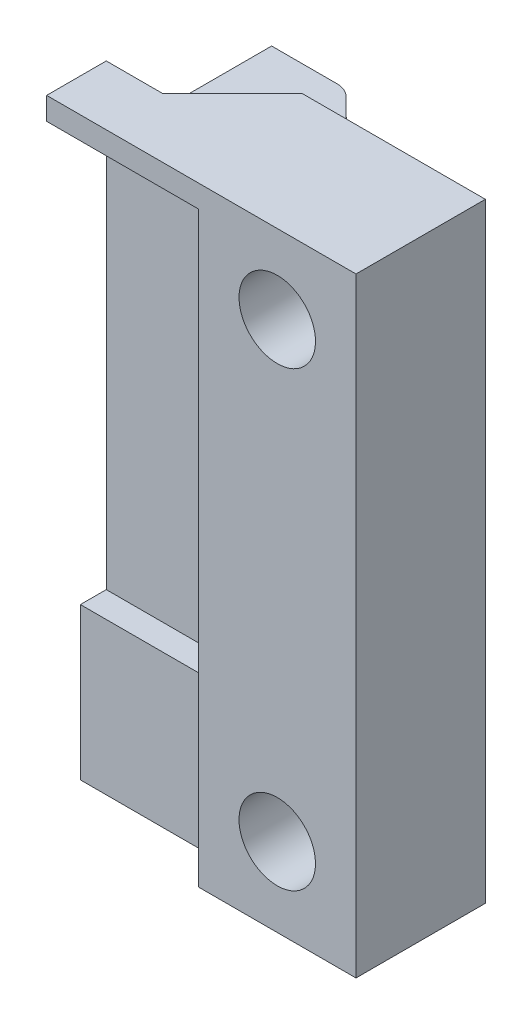
SolidWorks part; units mm, degrees
ref_plane "Front Plane" through (0, 0, 0) normal (0, 0, 1) x (1, 0, 0)
ref_plane "Top Plane" through (0, 0, 0) normal (0, 1, 0) x (1, 0, 0)
ref_plane "Right Plane" through (0, 0, 0) normal (1, 0, 0) x (0, 0, -1)
sketch "Sketch1" plane through (0, 0, 0) normal (0, 0, 1) x (1, 0, 0)
  line L0 (93.7285, 63.9679) -> (92.0785, 63.9679) construction
  line L1 (93.7285, 63.9679) -> (95.7285, 63.9679) construction
  line L2 (96.7285, 63.9679) -> (95.7285, 63.9679) construction
  line L3 (-96.2715, 63.9679) -> (-97.2715, 63.9679) construction
  line L4 (-96.2715, 63.9679) -> (-94.2715, 63.9679) construction
  line L5 (-92.6215, 63.9679) -> (-94.2715, 63.9679) construction
  line L6 (93.7285, 63.9679) -> (92.0785, 63.9679)
  line L7 (93.7285, 63.9679) -> (95.7285, 63.9679)
  line L8 (96.7285, 63.9679) -> (95.7285, 63.9679)
  line L9 (-96.2715, 63.9679) -> (-97.2715, 63.9679)
  line L10 (-96.2715, 63.9679) -> (-94.2715, 63.9679)
  line L11 (-92.6215, 63.9679) -> (-94.2715, 63.9679)
  line L12 (94.7285, 38.5679) -> (83.2213, 38.5679)
  line L13 (94.7285, 38.5679) -> (83.2213, 38.5679)
  line L14 (82.5285, 37.9679) -> (-69.3016, 37.9679)
  line L15 (82.5285, 37.9679) -> (-69.3016, 37.9679)
  line L16 (-69.3016, 37.9679) -> (-74.3016, 37.9679)
  line L17 (-69.3016, 37.9679) -> (-74.3016, 37.9679)
  line L18 (-74.3016, 37.9679) -> (-84.5715, 37.9679)
  line L19 (-74.3016, 37.9679) -> (-84.5715, 37.9679)
  line L20 (-84.5715, 37.9679) -> (-85.2715, 37.9679)
  line L21 (-84.5715, 37.9679) -> (-85.2715, 37.9679)
  line L22 (-85.2715, 37.9679) -> (-85.2715, 38.5679)
  line L23 (-85.2715, 37.9679) -> (-85.2715, 38.5679)
  line L24 (-85.2715, 38.5679) -> (-95.2715, 38.5679)
  line L25 (-85.2715, 38.5679) -> (-95.2715, 38.5679)
  line L26 (-97.2715, 40.5679) -> (-97.2715, 44.9679)
  line L27 (-97.2715, 40.5679) -> (-97.2715, 44.9679)
  line L28 (-97.2715, 44.9679) -> (-97.2715, 45.9679)
  line L29 (-97.2715, 44.9679) -> (-97.2715, 45.9679)
  line L30 (-97.2715, 45.9679) -> (-97.2715, 46.2179)
  line L31 (-97.2715, 45.9679) -> (-97.2715, 46.2179)
  line L32 (-97.2715, 46.2179) -> (-97.2715, 47.2179)
  line L33 (-97.2715, 46.2179) -> (-97.2715, 47.2179)
  line L34 (-97.2715, 47.2179) -> (-97.2715, 47.4679)
  line L35 (-97.2715, 47.2179) -> (-97.2715, 47.4679)
  line L36 (-97.2715, 47.4679) -> (-97.2715, 48.4679)
  line L37 (-97.2715, 47.4679) -> (-97.2715, 48.4679)
  line L38 (-97.2715, 48.4679) -> (-97.2715, 48.7179)
  line L39 (-97.2715, 48.4679) -> (-97.2715, 48.7179)
  line L40 (-97.2715, 48.7179) -> (-97.2715, 49.7179)
  line L41 (-97.2715, 48.7179) -> (-97.2715, 49.7179)
  line L42 (-97.2715, 49.7179) -> (-97.2715, 49.9679)
  line L43 (-97.2715, 49.7179) -> (-97.2715, 49.9679)
  line L44 (-97.2715, 49.9679) -> (-97.2715, 50.9679)
  line L45 (-97.2715, 49.9679) -> (-97.2715, 50.9679)
  line L46 (-97.2715, 50.9679) -> (-97.2715, 51.2179)
  line L47 (-97.2715, 50.9679) -> (-97.2715, 51.2179)
  line L48 (-97.2715, 51.2179) -> (-97.2715, 52.2179)
  line L49 (-97.2715, 51.2179) -> (-97.2715, 52.2179)
  line L50 (-97.2715, 52.2179) -> (-97.2715, 52.4679)
  line L51 (-97.2715, 52.2179) -> (-97.2715, 52.4679)
  line L52 (-97.2715, 52.4679) -> (-97.2715, 53.4679)
  line L53 (-97.2715, 52.4679) -> (-97.2715, 53.4679)
  line L54 (-97.2715, 53.4679) -> (-97.2715, 53.7179)
  line L55 (-97.2715, 53.4679) -> (-97.2715, 53.7179)
  line L56 (-97.2715, 53.7179) -> (-97.2715, 54.7179)
  line L57 (-97.2715, 53.7179) -> (-97.2715, 54.7179)
  line L58 (-97.2715, 54.7179) -> (-97.2715, 54.9679)
  line L59 (-97.2715, 54.7179) -> (-97.2715, 54.9679)
  line L60 (-97.2715, 54.9679) -> (-97.2715, 55.9679)
  line L61 (-97.2715, 54.9679) -> (-97.2715, 55.9679)
  line L62 (-97.2715, 55.9679) -> (-97.2715, 56.2179)
  line L63 (-97.2715, 55.9679) -> (-97.2715, 56.2179)
  line L64 (-97.2715, 56.2179) -> (-97.2715, 57.2179)
  line L65 (-97.2715, 56.2179) -> (-97.2715, 57.2179)
  line L66 (-97.2715, 57.2179) -> (-97.2715, 57.4679)
  line L67 (-97.2715, 57.2179) -> (-97.2715, 57.4679)
  line L68 (-97.2715, 57.4679) -> (-97.2715, 58.4679)
  line L69 (-97.2715, 57.4679) -> (-97.2715, 58.4679)
  line L70 (-97.2715, 58.4679) -> (-97.2715, 58.7179)
  line L71 (-97.2715, 58.4679) -> (-97.2715, 58.7179)
  line L72 (-97.2715, 58.7179) -> (-97.2715, 59.7179)
  line L73 (-97.2715, 58.7179) -> (-97.2715, 59.7179)
  line L74 (-97.2715, 59.7179) -> (-97.2715, 59.9679)
  line L75 (-97.2715, 59.7179) -> (-97.2715, 59.9679)
  line L76 (-97.2715, 59.9679) -> (-97.2715, 61.9679)
  line L77 (-97.2715, 59.9679) -> (-97.2715, 61.9679)
  line L78 (-97.2715, 61.9679) -> (-97.2715, 63.9679)
  line L79 (-97.2715, 61.9679) -> (-97.2715, 63.9679)
  line L80 (-97.2715, 63.9679) -> (96.7285, 63.9679)
  line L81 (-97.2715, 63.9679) -> (96.7285, 63.9679)
  line L82 (96.7285, 63.9679) -> (96.7285, 61.9679)
  line L83 (96.7285, 63.9679) -> (96.7285, 61.9679)
  line L84 (96.7285, 61.9679) -> (96.7285, 40.5679)
  line L85 (96.7285, 61.9679) -> (96.7285, 40.5679)
  arc A0 (82.5285, 37.9679) -> (83.2213, 38.5679) centre (82.5285, 38.6679) ccw
  arc A1 (82.5285, 37.9679) -> (83.2213, 38.5679) centre (82.5285, 38.6679) ccw
  arc A2 (-97.2715, 40.5679) -> (-95.2715, 38.5679) centre (-95.2715, 40.5679) ccw
  arc A3 (-97.2715, 40.5679) -> (-95.2715, 38.5679) centre (-95.2715, 40.5679) ccw
  arc A4 (94.7285, 38.5679) -> (96.7285, 40.5679) centre (94.7285, 40.5679) ccw
  arc A5 (94.7285, 38.5679) -> (96.7285, 40.5679) centre (94.7285, 40.5679) ccw
sketch "Sketch2" plane through (0, 0, 0) normal (0, 1, 0) x (1, 0, 0)
  line L30 (94, 0) -> (97, 0) construction
  line L54 (0, -21) -> (0, 21) construction
  line L56 (-94, 0) -> (-97, 0) construction
  line L57 (-94, -21) -> (94, -21) construction
  line L58 (-94, -21) -> (-94, 21) construction
  line L59 (-94, 21) -> (94, 21) construction
  line L60 (94, -21) -> (94, 21) construction
  line L61 (97, -27.5) -> (-97, -27.5) construction
  line L62 (97, -27.5) -> (97, 27.5) construction
  line L63 (97, 27.5) -> (-97, 27.5) construction
  line L64 (-97, -27.5) -> (-97, 27.5) construction
  line L65 (91, 24.625) -> (91, 17.375)
  line L66 (91, -24.625) -> (97, -24.625)
  line L67 (91, -24.625) -> (91, -17.375)
  line L68 (91, -17.375) -> (97, -17.375)
  line L69 (97, -24.625) -> (97, -17.375) construction
  line L70 (91, -24.625) -> (97, -17.375) construction
  line L71 (91, -17.375) -> (97, -24.625) construction
  line L72 (91, 24.625) -> (97, 24.625)
  line L73 (97, 24.625) -> (97, 17.375) construction
  line L74 (91, 17.375) -> (97, 17.375)
  line L75 (-91, -24.625) -> (-91, -17.375) construction
  line L76 (-91, -24.625) -> (-97, -24.625) construction
  line L77 (-97, -24.625) -> (-97, -17.375) construction
  line L78 (-91, -17.375) -> (-97, -17.375) construction
  line L79 (-91, 24.625) -> (-91, 17.375) construction
  line L80 (-91, 17.375) -> (-97, 17.375) construction
  line L81 (-97, 24.625) -> (-97, 17.375) construction
  line L82 (-91, 24.625) -> (-97, 24.625) construction
  line L84 (97, -24.625) -> (104.5, -24.625)
  line L85 (97, -24.625) -> (97, 27.5)
  line L86 (97, 27.5) -> (104.5, 27.5)
  line L87 (104.5, -24.625) -> (104.5, 27.5)
  circle A24 centre (94, -21) radius 2.125
  circle A25 centre (94, 21) radius 2.125
  circle A26 centre (-94, 21) radius 2.125 construction
  circle A27 centre (-94, -21) radius 2.125 construction
  point P28 (91.875, -21)
  point P31 (104.765, 27.5)
  dimension "D1" = 4.25
  dimension "D2" = 42
  dimension "D3" = 55
  dimension "D4" = 194
  dimension "D5" = 188
  dimension "D6" = 7.25
  dimension "D7" = 5.125
  dimension "D8" = 7.5
ref_plane "Plane1" through (91, 0, 24.625) normal (1, 0, 0) x (0, 0, -1)
sketch "Sketch3" plane through (91, 0, 0) normal (1, 0, 0) x (0, 0, -1)
  line L6 (-25.775, -17.25) -> (-24.625, -17.25)
  line L7 (-24.625, -17.25) -> (-24.625, 0)
  line L8 (-24.625, 0) -> (-17.275, 0)
  line L9 (-17.275, 0) -> (-17.275, -24)
  line L10 (-17.275, -24) -> (-25.775, -24)
  line L11 (-25.775, -24) -> (-25.775, -17.25)
  line L12 (-20.95, 0) -> (-20.95, 2.1) construction
  line L14 (-24.625, 3.1) -> (-27.275, 3.1)
  line L15 (-24.625, 3.1) -> (-24.625, 2.1)
  line L16 (-24.625, 2.1) -> (-27.275, 2.1)
  line L17 (-27.275, 3.1) -> (-27.275, 2.1)
  point P12 (0, 0)
  point P13 (-27.5794, 2.3293)
  dimension "D1" = 1.5
  dimension "D2" = 8.5
  dimension "D3" = 24
  dimension "D4" = 6.75
  dimension "D5" = 2.65
  dimension "D6" = 2.1
  dimension "D7" = 1
  dimension "D8" = 2.65
extrude "Boss-Extrude2" add sketch "Sketch3" along normal blind 6.75 separate body
sketch "Sketch4" plane through (0, 0, 0) normal (1, 0, 0) x (0, 0, -1)
  line L0 (-17.275, -24) -> (-25.775, -24) construction
  line L1 (-27.275, 3.1) -> (-21.525, 3.1)
  line L2 (-27.275, 3.1) -> (-27.275, -24)
  line L3 (-27.275, -24) -> (-21.525, -24)
  line L4 (-21.525, 3.1) -> (-21.525, -24)
  point P4 (0, 0)
  point P5 (0, 0)
  point P8 (0, 0)
  point P9 (-21.6703, -23.9413)
extrude "Boss-Extrude3" add sketch "Sketch4" along normal blind 7 from surface starting at face at (97.75, -13.75, 22.5583)
chamfer "Chamfer2" [suppressed] distance 4.25 angle 45
fillet "Fillet2" radius 0.5 1 edges at (94.375, 0, 24.625)
extrude "Cut-Extrude2" cut sketch "Sketch2" against normal blind 7 contours A24
sketch "Sketch6" plane through (0, 0, 0) normal (0, 1, 0) x (1, 0, 0)
  line L0 (97.75, -17.275) -> (102.815, -21.525)
  line L1 (102.815, -21.525) -> (97.75, -21.525)
  line L2 (97.75, -21.525) -> (97.75, -17.275)
  line L3 (104.75, -21.525) -> (97.75, -21.525) construction
  point P3 (0, 0)
  point P5 (0, 0)
  point P8 (0, 0)
  dimension "D1" = 40
extrude "Boss-Extrude4" add sketch "Sketch6" against normal up to surface (24 mm away) from surface up to face at (97.8125, -24, 22.9625) starting at face at (94, 0, 23.125)
sketch "Sketch5" plane through (0, 0, 21.525) normal (0, 0, -1) x (-1, 0, 0)
  line L1 (-101.25, 3.1) -> (-101.25, -24) construction
  line L2 (-104.75, 3.1) -> (-97.75, 3.1) construction
  line L4 (-104.75, -10.45) -> (-101.25, -10.45) construction
  line L5 (-104.75, -24) -> (-104.75, 3.1) construction
  circle A0 centre (-101.25, -0.4) radius 1.7
  circle A2 centre (-101.25, -0.4) radius 3.5 construction
  circle A3 centre (-101.25, -20.5) radius 1.7
  point P16 (0, 0)
  dimension "D1" = 3.4
  dimension "D2" = 7
extrude "Cut-Extrude1" cut sketch "Sketch5" against normal through all both and the other way through all
chamfer "Chamfer3" distance 4.25 angle 45 1 edges at (97.75, 2.6, 24.625)
sketch "Sketch7" plane through (0, 0, 21.525) normal (0, 0, -1) x (-1, 0, 0)
  circle A0 centre (-101.25, -0.4) radius 2.7
  circle A1 centre (-101.25, -20.5) radius 1.7
  circle A2 centre (-101.25, -20.5) radius 1.7 construction
  circle A3 centre (-101.25, -0.4) radius 1.7
  circle A4 centre (-101.25, -0.4) radius 1.7 construction
  circle A5 centre (-101.25, -20.5) radius 2.7
  dimension "D1" = 0
  dimension "D2" = 0
  dimension "D3" = 1
extrude "Cut-Extrude3" cut sketch "Sketch7" along normal blind 7 draft 45 draft outward yes
fillet "Fillet3" radius 1 4 edges at (95.1267, -3.6876, 17.275) (94.5294, -18.7291, 17.275) (100.8539, -16.1726, 19.8795) (100.8539, -4.7274, 19.8795)
